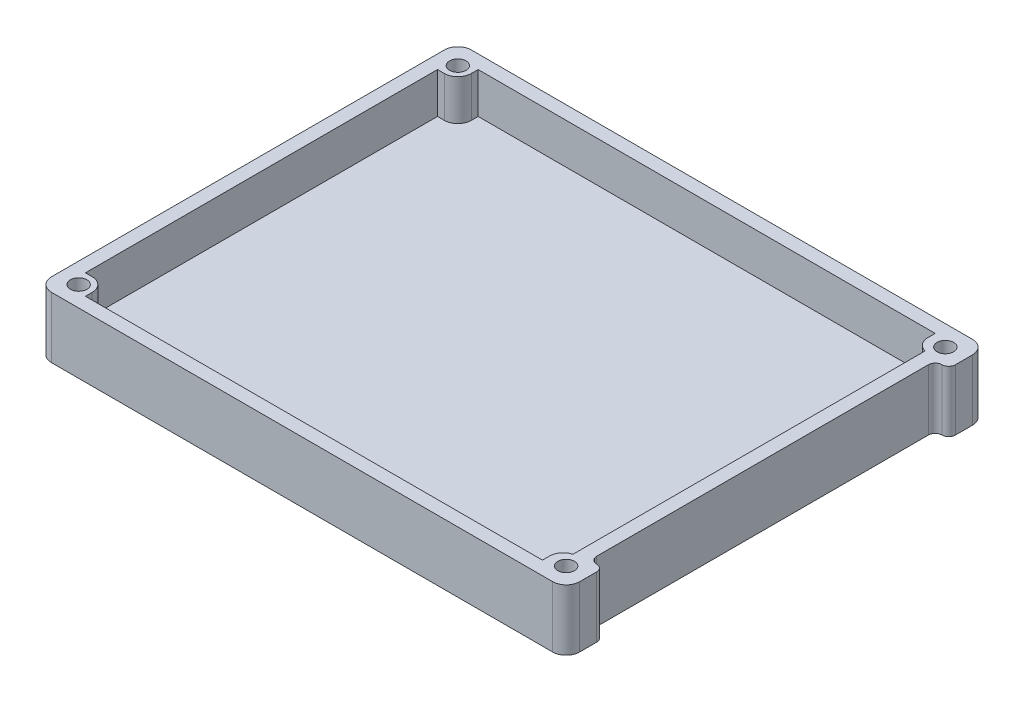
SolidWorks part; units mm, degrees
ref_plane "Front" through (0, 0, 0) normal (0, 0, 1) x (1, 0, 0)
ref_plane "Top" through (0, 0, 0) normal (0, 1, 0) x (1, 0, 0)
ref_plane "Right" through (0, 0, 0) normal (1, 0, 0) x (0, 0, -1)
sketch "Sketch3" plane through (0, 0, 0) normal (0, -1, 0) x (1, 0, 0)
  line L0 (-37.5, -31) -> (40.5, 31) construction
  line L1 (-37.5, 31) -> (40.5, 31)
  line L2 (-37.5, 31) -> (-37.5, -31)
  line L3 (-37.5, -31) -> (40.5, -31)
  line L4 (40.5, 31) -> (40.5, 25.5)
  line L5 (-37.5, 31) -> (40.5, -31) construction
  line L6 (35.8, 27.65) -> (-35.8, -27.65) construction
  line L7 (35.8, 27.65) -> (-35.8, 27.65) construction
  line L8 (35.8, 27.65) -> (35.8, -27.65) construction
  line L9 (35.8, -27.65) -> (-35.8, -27.65) construction
  line L10 (-35.8, 27.65) -> (-35.8, -27.65) construction
  line L11 (-35.8, -27.65) -> (-35.8, 27.65) construction
  line L12 (-35.8, 27.65) -> (35.8, -27.65) construction
  line L13 (40.5, 25.5) -> (38.5, 25.5)
  line L14 (38.5, 25.5) -> (38.5, -25.5)
  line L15 (38.5, -25.5) -> (40.5, -25.5)
  line L16 (40.5, -25.5) -> (40.5, -31)
  line L17 (59.9246, 0) -> (-71.6473, 0) construction
  point P0 (0, 0)
  point P5 (1.5, 0)
  point P18 (40.5, 28.25)
  dimension "D1" = 78
  dimension "D2" = 62
  dimension "D3" = 71.6
  dimension "D4" = 55.3
  dimension "D5" = 1.5
  dimension "D6" = 5.5
  dimension "D7" = 2
extrude "Boss-Extrude2" add sketch "Sketch3" along normal blind 3
sketch "Sketch4" plane through (0, 0, 0) normal (0, 1, 0) x (1, 0, 0)
  line L0 (-37.5, -31) -> (-37.5, 31) construction
  line L1 (-37.5, -31) -> (40.5, -31)
  line L2 (-37.5, -31) -> (-37.5, 31)
  line L3 (-37.5, 31) -> (40.5, 31)
  line L4 (40.5, -31) -> (40.5, -25.5)
  line L5 (-32.5, -29) -> (35, -29)
  line L6 (-35.5, -26) -> (-35.5, 26)
  line L7 (-32.5, 29) -> (35, 29)
  line L8 (36.5, -26) -> (36.5, 26)
  line L9 (40.5, -31) -> (-37.5, -31) construction
  line L10 (40.5, 25.5) -> (38.5, 25.5)
  line L11 (38.5, 25.5) -> (38.5, -25.5)
  line L12 (38.5, -25.5) -> (40.5, -25.5)
  line L13 (36.5, -26) -> (35, -26)
  line L14 (35, -29) -> (35, -26)
  line L15 (38.5, 25.5) -> (38.5, -25.5) construction
  line L17 (-35.5, -26) -> (-32.5, -26)
  line L18 (-32.5, -29) -> (-32.5, -26)
  line L19 (40.5, 25.5) -> (40.5, 31)
  line L20 (-37.5, 31) -> (40.5, 31) construction
  line L21 (-35.5, 26) -> (-32.5, 26)
  line L22 (-32.5, 29) -> (-32.5, 26)
  line L25 (36.5, 26) -> (35, 26)
  line L26 (35, 29) -> (35, 26)
  dimension "D5" = 3
  dimension "D1" = 2
  dimension "D2" = 2
  dimension "D3" = 2
  dimension "D4" = 2
  dimension "D6" = 1.5
  dimension "D7" = 3
extrude "Boss-Extrude3" add sketch "Sketch4" along normal blind 6
fillet "Fillet5" radius 2 4 edges at (-32.5, 3, -26) (35, 3, -26) (-32.5, 3, 26) (35, 3, 26)
hole_wizard "CSK for #2 Flat Head Socket Cap Screw1" positions "Sketch20" profile "Sketch22" countersink size "#2" standard "ANSI Inch" end condition up to next
sketch "Sketch20" plane through (0, -3, 0) normal (0, -1, 0) x (-1, 0, 0)
  line L1 (-37.5, 28) -> (34.5, 28)
  line L2 (-37.5, 28) -> (-37.5, -28)
  line L3 (-37.5, -28) -> (34.5, -28)
  line L4 (34.5, 28) -> (34.5, -28)
  line L8 (-40.5, -25.5) -> (-40.5, -31) construction
  line L9 (-40.5, 31) -> (37.5, 31) construction
  line L10 (37.5, -31) -> (37.5, 31) construction
  line L11 (-40.5, -31) -> (37.5, -31) construction
  point P0 (-37.5, 28)
  point P2 (34.5, 28)
  point P4 (34.5, -28)
  point P6 (-37.5, -28)
  dimension "D1" = 3
  dimension "D2" = 3
  dimension "D3" = 3
  dimension "D4" = 3
sketch "Sketch22" plane through (37.5, -3, -28) normal (1, 0, 0) x (0, 0, -1)
  line L0 (0, 0) -> (0, 9)
  line L1 (0, 9) -> (1.2192, 9)
  line L2 (1.2192, 9) -> (1.2192, 1.4756)
  line L3 (1.2192, 1.4756) -> (2.5019, 0)
  line L5 (2.5019, 0) -> (0, 0)
  line L6 (-1.2192, 1.4756) -> (-2.5019, 0) construction
  line L11 (0, -6.35) -> (0, 107.95) construction
  dimension "Thru Hole Dia." = 2.4384
  dimension "Thru Hole Depth" = 9
  dimension "Near C'Sink Dia." = 5.0038
  dimension "Near C'Sink Angle" = 82
fillet "Fillet6" radius 2 4 edges at (-37.5, 1.5, -31) (40.5, 1.5, 31) (-37.5, 1.5, 31) (40.5, 1.5, -31)
fillet "Fillet7" radius 1 4 edges at (38.5, 1.5, -25.5) (40.5, 1.5, -25.5) (40.5, 1.5, 25.5) (38.5, 1.5, 25.5)
equation "\"D2@Sketch4\"=\"D1@Sketch4\""
equation "\"D3@Sketch4\"=\"D1@Sketch4\""
equation "\"D4@Sketch20\"=\"D2@Sketch20\""
equation "\"D3@Sketch20\"=\"D2@Sketch20\""
equation "\"D1@Sketch20\"=\"D2@Sketch20\""
